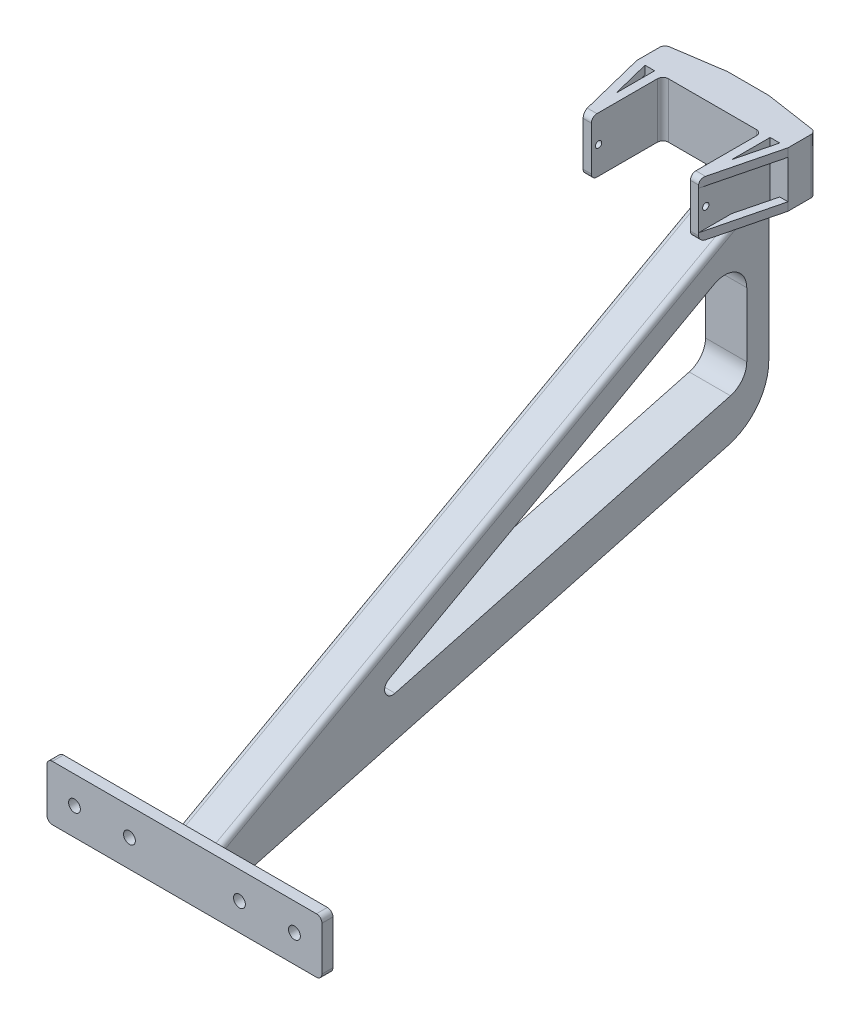
SolidWorks part; units mm, degrees
material "Balsa"
ref_plane "前视基准面" through (0, 0, 0) normal (0, 0, 1) x (1, 0, 0)
ref_plane "上视基准面" through (0, 0, 0) normal (0, 1, 0) x (1, 0, 0)
ref_plane "右视基准面" through (0, 0, 0) normal (1, 0, 0) x (0, 0, -1)
other "Configuration Table"
sketch "Sketch1" plane through (0, 0, 0) normal (0, 0, 1) x (1, 0, 0)
  line L0 (50, 20) -> (50, 0) construction
  line L1 (0, 0) -> (100, 0)
  line L2 (0, 0) -> (0, 20)
  line L3 (0, 20) -> (100, 20)
  line L4 (100, 0) -> (100, 20)
  circle A0 centre (70, 10) radius 2.15
  circle A1 centre (30, 10) radius 2.15
  circle A2 centre (10, 10) radius 2.15
  circle A3 centre (90, 10) radius 2.15
  dimension "D3" = 4.3
  dimension "D6" = 20
  dimension "D7" = 4.3
  dimension "D1" = 100
  dimension "D2" = 20
  dimension "D4" = 40
  dimension "D5" = 10
extrude "Boss-Extrude1" add sketch "Sketch1" along normal blind 4
ref_plane "Plane1" through (50, 0, 0) normal (-1, 0, 0) x (0, 0, 1)
sketch "Sketch4" plane through (50, 0, 0) normal (-1, 0, 0) x (0, 0, 1)
  line L0 (0, 20) -> (0, 0) construction
  line L1 (4, 0) -> (0, 0) construction
  line L2 (4, 20) -> (4, 0) construction
  line L3 (4, 20) -> (0, 20) construction
  line L4 (0, 20) -> (0, 0)
  line L5 (4, 0) -> (0, 0)
  line L6 (4, 20) -> (4, 0)
  line L7 (4, 20) -> (0, 20)
  line L8 (4, 10) -> (0, 10) construction
  line L9 (-1, 17.5) -> (-193, 68.9462)
  line L10 (0, 17.5) -> (-1, 17.5)
  line L11 (0, 17.5) -> (0, 2.5)
  line L12 (0, 2.5) -> (-1, 2.5)
  line L13 (-1, 17.5) -> (-1, 2.5)
  line L14 (-193, 68.9462) -> (-193, 155)
  line L15 (-193, 155) -> (-201, 155)
  line L16 (-201, 155) -> (-201, 56.0898)
  line L17 (-201, 56.0898) -> (-1, 2.5)
  line L18 (-193, 111.9731) -> (-41.2714, 28.2907)
  line L19 (-193, 123.3932) -> (-1, 17.5)
  dimension "D1" = 15
  dimension "D2" = 7.5
  dimension "D3" = 1
  dimension "D4" = 145
  dimension "D5" = 200
  dimension "D6" = 8
  dimension "D7" = 75
  dimension "D8" = 10
extrude "Boss-Extrude2" add sketch "Sketch4" along normal mid plane 15 separate body contours L16 L17 L13 L9 L14 L15 | L19 L14 L18 L9 | L11 L10 L13 L12 region at (50, 10, -3.5151) region at (50, 70.2954, -106.6747)
fillet "Fillet1" radius 8 2 edges at (50, 111.9731, -193) (50, 68.9462, -193)
fillet "Fillet2" radius 3 1 edges at (50, 28.2907, -41.2714)
fillet "Fillet3" radius 20 1 edges at (50, 56.0898, -201)
sketch "Sketch5" plane through (0, 0, -193) normal (0, 0, 1) x (1, 0, 0)
  line L0 (50, 123.3932) -> (50, 155) construction
  line L1 (32, 155) -> (68, 155)
  line L2 (32, 155) -> (32, 135)
  line L3 (32, 135) -> (68, 135)
  line L4 (68, 155) -> (68, 135)
  line L5 (42.5, 123.3932) -> (57.5, 123.3932) construction
  line L8 (42.5, 155) -> (57.5, 155) construction
  line L9 (42.5, 155) -> (57.5, 155)
  line L11 (22.5, 155) -> (77.5, 155)
  line L12 (22.5, 155) -> (22.5, 135)
  line L13 (22.5, 135) -> (77.5, 135)
  line L14 (77.5, 155) -> (77.5, 135)
  line M11 (57.5, 123.3932) -> (57.5, 155)
  line M12 (57.5, 155) -> (42.5, 155)
  line M13 (42.5, 155) -> (42.5, 123.3932)
  dimension "D1" = 20
  dimension "D2" = 36
  dimension "D3" = 18
  dimension "D4" = 55
  dimension "D5" = 27.5
extrude "Boss-Extrude3" add sketch "Sketch5" along normal mid plane 10 contours L12 L13 L2 L11 | L2 L3 L1 M13 | L3 L0 L11 M13 | L0 L13 M11 M12 | L4 L1 L3 M11 | L14 L11 L4 L13 region at (46.25, 145, -193) region at (53.75, 145, -193) region at (37.25, 145, -193) region at (62.75, 145, -193) region at (27.25, 145, -193) region at (72.75, 145, -193)
sketch "Sketch6" plane through (0, 0, -188) normal (0, 0, 1) x (1, 0, 0)
  line L0 (42.5, 155) -> (57.5, 155) construction
  line L1 (42.5, 155) -> (57.5, 155)
  line L3 (32, 155) -> (29, 155)
  line L4 (77.5, 155) -> (22.5, 155)
  line L5 (77.5, 135) -> (77.5, 155)
  line L6 (22.5, 135) -> (77.5, 135)
  line L7 (22.5, 155) -> (22.5, 135)
  line L8 (77.5, 155) -> (22.5, 155)
  line L9 (77.5, 135) -> (77.5, 155)
  line L10 (22.5, 135) -> (77.5, 135)
  line L11 (22.5, 155) -> (22.5, 135)
  line L12 (68, 155) -> (32, 155)
  line L13 (68, 135) -> (68, 155)
  line L14 (32, 135) -> (68, 135)
  line L15 (32, 155) -> (32, 135)
  line L16 (68, 155) -> (32, 155)
  line L17 (68, 135) -> (68, 155)
  line L18 (32, 135) -> (68, 135)
  line L19 (32, 155) -> (32, 135)
  line L20 (32, 155) -> (32, 135)
  line L21 (32, 135) -> (29, 135)
  line L22 (29, 155) -> (29, 135)
  line L23 (68, 155) -> (71, 155)
  line L24 (68, 155) -> (68, 135)
  line L25 (68, 135) -> (71, 135)
  line L26 (71, 155) -> (71, 135)
  line M20 (77.5, 155) -> (22.5, 155)
  dimension "D3" = 3
  dimension "D4" = 3
  dimension "D1" = 0
  dimension "D2" = 0
extrude "Boss-Extrude4" add sketch "Sketch6" along normal blind 26 contours L22 L10 L19 M20 | L26 L8 L17 L10 region at (30.5, 145, -188) region at (69.5, 145, -188)
sketch "Sketch8" plane through (0, 155, 0) normal (0, 1, 0) x (1, 0, 0)
  line L0 (50, 188) -> (50, 112) construction
  line L1 (32, 188) -> (68, 188) construction
  line L2 (22.5, 188) -> (29, 162)
  line L3 (29, 162) -> (29, 174)
  line L4 (29, 162) -> (29, 188) construction
  line L5 (29, 174) -> (25.5, 188)
  line L6 (22.5, 188) -> (29, 188) construction
  line L7 (25.5, 188) -> (22.5, 188)
  line L8 (74.5, 188) -> (77.5, 188)
  line L9 (71, 174) -> (74.5, 188)
  line L10 (71, 162) -> (71, 174)
  line L11 (77.5, 188) -> (71, 162)
  dimension "D1" = 3
extrude "Boss-Extrude5" add sketch "Sketch8" against normal blind 3
pattern_linear "LPattern2" count 2 spacing 17 along (0, -1, 0) of "Boss-Extrude5"
sketch "Sketch9" plane through (71, 0, 0) normal (1, 0, 0) x (0, 0, -1)
  line L0 (174, 152) -> (162, 152) construction
  line L1 (188, 152) -> (188, 138) construction
  circle A0 centre (164.6, 145) radius 1.15
  dimension "D2" = 23.4
  dimension "D3" = 2.3
  dimension "D1" = 7
extrude "Cut-Extrude1" cut sketch "Sketch9" against normal through all
sketch "Sketch10" plane through (0, 155, 0) normal (0, 1, 0) x (1, 0, 0)
  line L3 (57.5, 201) -> (57.5, 198)
  line L4 (57.5, 198) -> (77.5, 198)
  line L5 (77.5, 198) -> (57.5, 201)
  line L6 (42.5, 201) -> (42.5, 198)
  line L7 (42.5, 198) -> (22.5, 198)
  line L8 (22.5, 198) -> (42.5, 201)
extrude "Boss-Extrude6" add sketch "Sketch10" against normal up to surface (20 mm away) up to face at (72.1667, 135, -183.3333)
fillet "Fillet4" radius 2 4 edges at (68, 145, -188) (32, 145, -188) (77.5, 145, -198) (22.5, 145, -198)
chamfer "Chamfer1" distance 3 angle 45 1 edges at (50, 135, -193)
chamfer "Chamfer2" distance 5 angle 45 2 edges at (57.5, 135, -195.5) (42.5, 135, -195.5)
fillet "Fillet5" radius 2 4 edges at (69.5, 155, -162) (69.5, 135, -162) (30.5, 135, -162) (30.5, 155, -162)
fillet "Fillet6" radius 2 4 edges at (100, 20, 2) (100, 0, 2) (0, 0, 2) (0, 20, 2)
sketch "Sketch11" plane through (0, 17.5, 0) normal (0, 1, 0) x (1, 0, 0)
  line L0 (57.5, 1) -> (57.5, 0)
  line L1 (42.5, 0) -> (57.5, 0) construction
  line L2 (57.5, 0) -> (66.5, 0)
  line L3 (66.5, 0) -> (57.5, 1)
  line L4 (42.5, 1) -> (42.5, 0)
  line L5 (42.5, 0) -> (33.5, 0)
  line L6 (98, 0) -> (2, 0) construction
  line L7 (33.5, 0) -> (42.5, 1)
  dimension "D1" = 9
  dimension "D2" = 9
extrude "Boss-Extrude7" add sketch "Sketch11" against normal up to surface (15 mm away) up to face at (50, 2.5, -0.5)
fillet "Fillet7" radius 2 2 edges at (57.5, 70.4466, -97) (42.5, 70.4466, -97)
